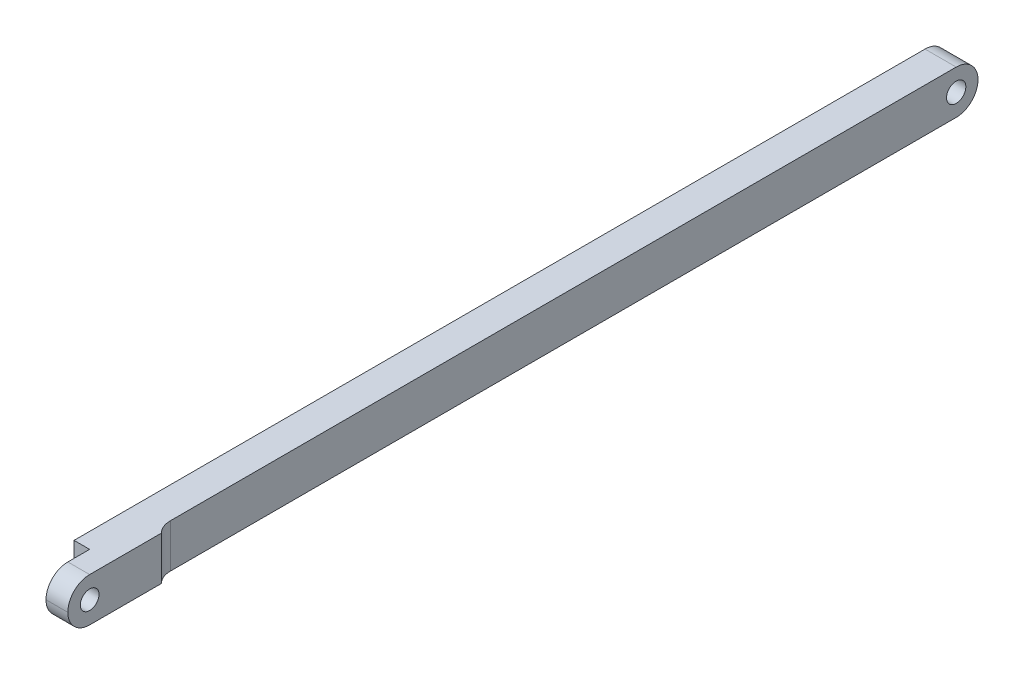
SolidWorks part; units mm, degrees
ref_plane "前视基准面" through (0, 0, 0) normal (0, 0, 1) x (1, 0, 0)
ref_plane "上视基准面" through (0, 0, 0) normal (0, 1, 0) x (1, 0, 0)
ref_plane "右视基准面" through (0, 0, 0) normal (1, 0, 0) x (0, 0, -1)
sketch "草图1" plane through (0, 0, 0) normal (0, 0, 1) x (1, 0, 0)
  line L1 (-2.5, 3.5) -> (2.5, 3.5)
  line L2 (-2.5, 3.5) -> (-2.5, -3.5)
  line L3 (-2.5, -3.5) -> (2.5, -3.5)
  line L4 (2.5, 3.5) -> (2.5, -3.5)
  line L5 (-2.5, 3.5) -> (2.5, -3.5) construction
  line L6 (-2.5, -3.5) -> (2.5, 3.5) construction
  point P0 (0, 0)
  dimension "D1" = 5
  dimension "D2" = 7
extrude "凸台-拉伸2" add sketch "草图1" along normal blind 140
fillet "圆角1" radius 3.5 2 edges at (0, -3.5, 0) (0, 3.5, 0)
sketch "草图3" plane through (2.5, 0, 0) normal (1, 0, 0) x (0, 0, -1)
  circle A0 centre (-3.5, 0) radius 1.55
  dimension "D1" = 3.1
extrude "切除-拉伸1" cut sketch "草图3" against normal through all
sketch "草图4" plane through (0, 0, 140) normal (0, 0, 1) x (1, 0, 0)
  line L0 (2.5, 3.5) -> (0, 3.5)
  line L1 (2.5, 3.5) -> (-2.5, 3.5) construction
  line L2 (0, 3.5) -> (0, -3.5)
  line L5 (0, -3.5) -> (2.5, -3.5)
  line L6 (2.5, -3.5) -> (2.5, 3.5)
  dimension "D1" = 2.5
extrude "凸台-拉伸3" add sketch "草图4" along normal blind 7
sketch "草图5" plane through (2.5, 0, 0) normal (1, 0, 0) x (0, 0, -1)
  line L0 (-147, -3.5) -> (-3.5, -3.5) construction
  line L1 (-147, 3.5) -> (-132, 3.5)
  line L2 (-147, 3.5) -> (-147, -3.5)
  line L3 (-147, -3.5) -> (-132, -3.5)
  line L4 (-132, 3.5) -> (-132, -3.5)
  dimension "D1" = 15
extrude "凸台-拉伸4" add sketch "草图5" along normal blind 1
fillet "圆角2" radius 3.5 2 edges at (1.75, -3.5, 147) (1.75, 3.5, 147)
sketch "草图6" plane through (0, 0, 0) normal (-1, 0, 0) x (0, 0, 1)
  circle A0 centre (143.5, 0) radius 1.5
  dimension "D1" = 3
extrude "切除-拉伸2" cut sketch "草图6" against normal through all
fillet "圆角3" radius 3.5 1 edges at (2.5, 0, 132)
